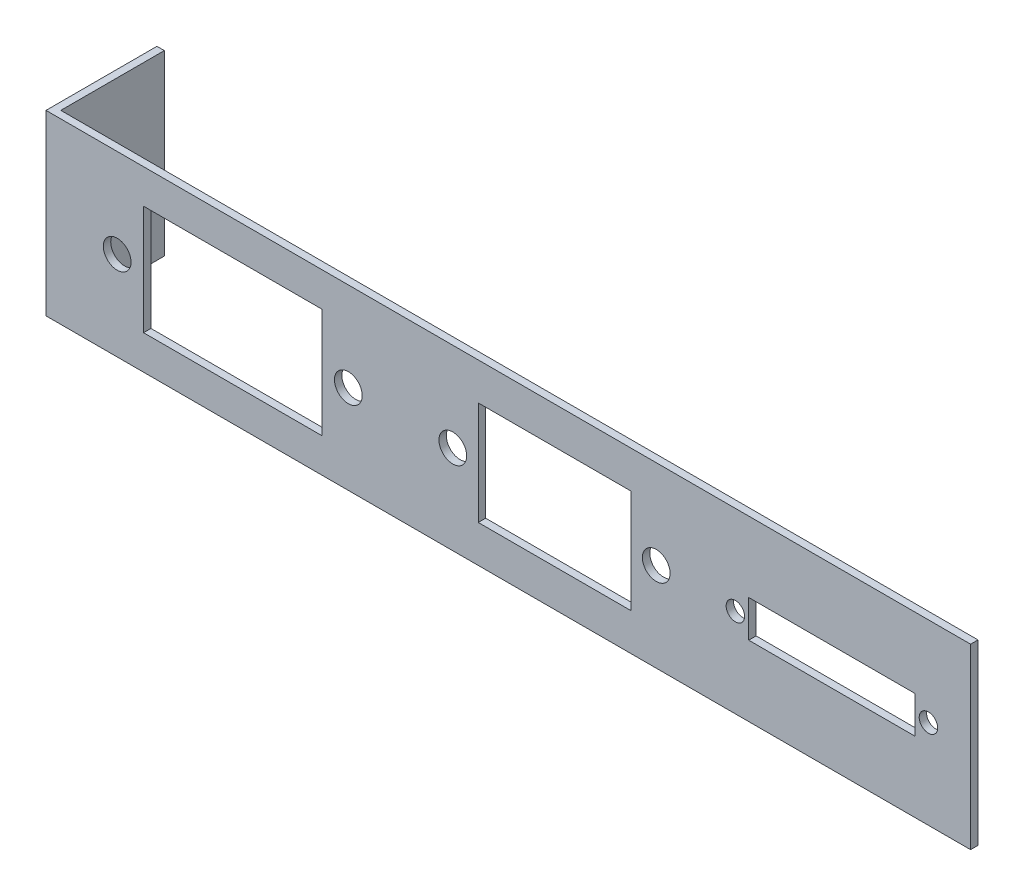
SolidWorks part; units mm, degrees
ref_plane "Front Plane" through (0, 0, 0) normal (0, 0, 1) x (1, 0, 0)
ref_plane "Top Plane" through (0, 0, 0) normal (0, 1, 0) x (1, 0, 0)
ref_plane "Right Plane" through (0, 0, 0) normal (1, 0, 0) x (0, 0, -1)
sketch "Sketch1" plane through (0, 0, 0) normal (0, 0, 1) x (1, 0, 0)
  line L1 (-50, -9.625) -> (50, -9.625)
  line L2 (-50, -9.625) -> (-50, 9.625)
  line L3 (-50, 9.625) -> (50, 9.625)
  line L4 (50, -9.625) -> (50, 9.625)
  line L5 (-50, -9.625) -> (50, 9.625) construction
  line L6 (-50, 9.625) -> (50, -9.625) construction
  point P0 (0, 0)
  dimension "D1" = 19.25
  dimension "D2" = 100
extrude "Boss-Extrude1" add sketch "Sketch1" along normal blind 0.8
sketch "Sketch2" plane through (0, 0, 0.8) normal (0, 0, -1) x (-1, 0, 0)
  line L0 (50, -9.625) -> (-50, -9.625) construction
  line L1 (50, 9.625) -> (49.2, 9.625)
  line L2 (50, 9.625) -> (50, -9.625)
  line L3 (50, -9.625) -> (49.2, -9.625)
  line L4 (49.2, 9.625) -> (49.2, -9.625)
  dimension "D1" = 0.8
extrude "Boss-Extrude2" add sketch "Sketch2" along normal blind 12
sketch "Sketch3" plane through (0, 0, 0.8) normal (0, 0, 1) x (1, 0, 0)
  line L0 (-50, 9.625) -> (-50, -9.625) construction
  line L1 (-42.3, 0) -> (-17.3, 0) construction
  line L2 (-39.45, -5.925) -> (-20.15, -5.925)
  line L3 (-39.45, -5.925) -> (-39.45, 5.925)
  line L4 (-39.45, 5.925) -> (-20.15, 5.925)
  line L5 (-20.15, -5.925) -> (-20.15, 5.925)
  line L6 (-39.45, -5.925) -> (-20.15, 5.925) construction
  line L7 (-39.45, 5.925) -> (-20.15, -5.925) construction
  circle A0 centre (-42.3, 0) radius 1.5
  circle A1 centre (-17.3, 0) radius 1.5
  point P4 (-29.8, 0)
  point P8 (-29.8, 0)
  dimension "D2" = 3
  dimension "D3" = 25
  dimension "D1" = 7.7
  dimension "D4" = 11.85
  dimension "D5" = 19.3
extrude "XT60 cutout" cut sketch "Sketch3" against normal through all
sketch "Sketch5" plane through (0, 0, 0.8) normal (0, 0, 1) x (1, 0, 0)
  line L1 (-6, 0) -> (16, 0) construction
  line L2 (-3.25, -5.6) -> (13.25, -5.6)
  line L3 (-3.25, -5.6) -> (-3.25, 5.6)
  line L4 (-3.25, 5.6) -> (13.25, 5.6)
  line L5 (13.25, -5.6) -> (13.25, 5.6)
  line L6 (-3.25, -5.6) -> (13.25, 5.6) construction
  line L7 (-3.25, 5.6) -> (13.25, -5.6) construction
  line L8 (-50, 9.625) -> (-50, -9.625) construction
  circle A0 centre (-6, 0) radius 1.5
  circle A1 centre (16, 0) radius 1.5
  point P2 (7.6207, -1.212)
  point P4 (5, 0)
  point P8 (5, 0)
  dimension "D2" = 3
  dimension "D3" = 22
  dimension "D1" = 55
  dimension "D4" = 11.2
  dimension "D5" = 16.5
extrude "Cut-Extrude4" cut sketch "Sketch5" against normal through all and the other way through all
sketch "Sketch6" plane through (0, 0, 0.8) normal (0, 0, 1) x (1, 0, 0)
  line L0 (24.56, 0) -> (45.44, 0) construction
  line L1 (26, -2) -> (44, -2)
  line L2 (26, -2) -> (26, 2)
  line L3 (26, 2) -> (44, 2)
  line L4 (44, -2) -> (44, 2)
  line L5 (26, -2) -> (44, 2) construction
  line L6 (26, 2) -> (44, -2) construction
  circle A0 centre (45.44, 0) radius 1
  circle A1 centre (24.56, 0) radius 1
  point P0 (35, 0)
  point P11 (48.6051, 0)
  point P12 (35, 0)
  point P13 (46.7176, 0)
  dimension "D4" = 2
  dimension "D1" = 18
  dimension "D2" = 4
  dimension "D3" = 85
  dimension "D5" = 20.88
extrude "Cut-Extrude5" cut sketch "Sketch6" against normal through all
